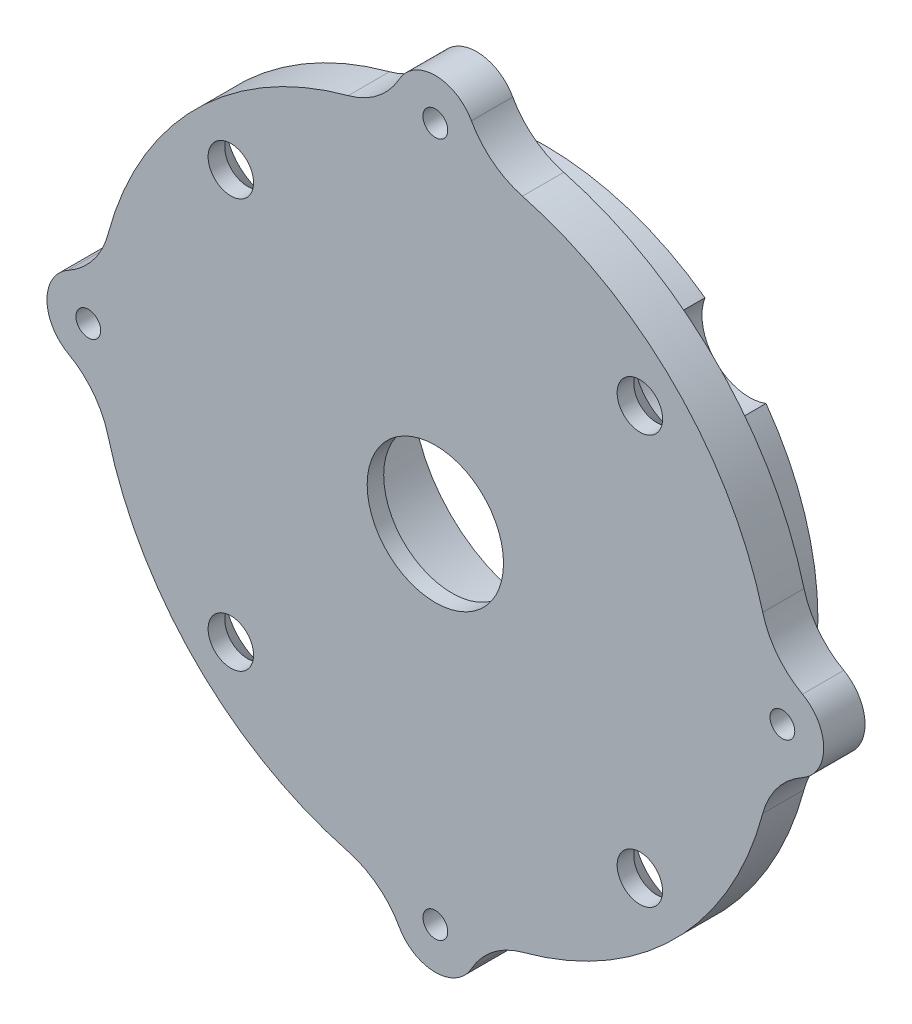
SolidWorks part; units mm, degrees
ref_plane "Ön Düzlem" through (0, 0, 0) normal (0, 0, 1) x (1, 0, 0)
ref_plane "Üst Düzlem" through (0, 0, 0) normal (0, 1, 0) x (1, 0, 0)
ref_plane "Sağ Düzlem" through (0, 0, 0) normal (1, 0, 0) x (0, 0, -1)
sketch "Çizim1" plane through (0, 0, 0) normal (0, 0, 1) x (1, 0, 0)
  circle A0 centre (0, 0) radius 16.1
  circle A1 centre (0, 0) radius 22.5
  circle A2 centre (0, 0) radius 33.05
  circle A3 centre (0, 0) radius 28
  dimension "D1" = 32.2
  dimension "D2" = 45
  dimension "D3" = 66.1
  dimension "D4" = 56
extrude "Yükseklik-Ekstrüzyon1" add sketch "Çizim1" along normal blind 8.25 contours A1 A0 | A2 A3 region at (-21.8636, 0, 0) region at (-32.1152, 0, 0)
sketch "Çizim2" plane through (0, 0, 8.25) normal (0, 0, 1) x (1, 0, 0)
  circle A0 centre (-24.75, 24.75) radius 2
  circle A1 centre (24.75, 24.75) radius 2
  circle A2 centre (24.75, -24.75) radius 2
  circle A3 centre (-24.75, -24.75) radius 2
  arc A6 (-10.5408, 39.6218) -> (-39.6218, 10.5408) centre (0, 0) ccw
  circle A7 centre (0, 42) radius 1.5
  arc A8 (4.3706, 44.4286) -> (-4.3706, 44.4286) centre (0, 42) ccw
  arc A9 (-4.3706, 44.4286) -> (-10.5408, 39.6218) centre (-13.1118, 49.2857) cw
  arc A10 (4.3706, 44.4286) -> (10.5408, 39.6218) centre (13.1118, 49.2857) ccw
  arc A11 (44.4286, 4.3706) -> (39.6218, 10.5408) centre (49.2857, 13.1118) cw
  arc A12 (44.4286, -4.3706) -> (44.4286, 4.3706) centre (42, 0) ccw
  circle A13 centre (42, 0) radius 1.5
  arc A14 (44.4286, -4.3706) -> (39.6218, -10.5408) centre (49.2857, -13.1118) ccw
  arc A15 (4.3706, -44.4286) -> (10.5408, -39.6218) centre (13.1118, -49.2857) cw
  arc A16 (-4.3706, -44.4286) -> (4.3706, -44.4286) centre (0, -42) ccw
  circle A17 centre (0, -42) radius 1.5
  arc A18 (-4.3706, -44.4286) -> (-10.5408, -39.6218) centre (-13.1118, -49.2857) ccw
  arc A19 (-44.4286, -4.3706) -> (-39.6218, -10.5408) centre (-49.2857, -13.1118) cw
  arc A20 (-44.4286, 4.3706) -> (-44.4286, -4.3706) centre (-42, 0) ccw
  circle A21 centre (-42, 0) radius 1.5
  arc A22 (-44.4286, 4.3706) -> (-39.6218, 10.5408) centre (-49.2857, 13.1118) ccw
  arc A23 (-39.6218, -10.5408) -> (-10.5408, -39.6218) centre (0, 0) ccw
  arc A24 (10.5408, -39.6218) -> (39.6218, -10.5408) centre (0, 0) ccw
  arc A25 (39.6218, 10.5408) -> (10.5408, 39.6218) centre (0, 0) ccw
  circle A26 centre (0, 0) radius 8.25
  point P0 (0, 0)
  point P17 (0, 0)
  point P48 (0, 0)
  dimension "D3" = 4
  dimension "D4" = 24.75
  dimension "D5" = 24.75
  dimension "D1" = 82
  dimension "D2" = 42
  dimension "D7" = 10
  dimension "D8" = 3
  dimension "D9" = 10
  dimension "D10" = 10
  dimension "D12" = 16.5
  dimension "D6" = 4
  dimension "D11" = 4
extrude "Yükseklik-Ekstrüzyon2" add sketch "Çizim2" along normal blind 5
hole_wizard "M5 Altıgen Alyan Havşa Başlı Vida İçin Havşa1" positions "3B Çizim1" profile "Çizim5" countersink size "M5" standard "DIN" end condition through all
sketch3d "3B Çizim1"
  line L0 (24.75, 24.75, 13.25) -> (24.75, 24.75, 8.25) construction
  line L1 (-24.75, 24.75, 13.25) -> (-24.75, 24.75, 8.25) construction
  line L2 (-24.75, -24.75, 13.25) -> (-24.75, -24.75, 8.25) construction
  line L3 (24.75, -24.75, 13.25) -> (24.75, -24.75, 8.25) construction
  point P0 (24.75, 24.75, 8.25)
  point P4 (-24.75, 24.75, 8.25)
  point P8 (-24.75, -24.75, 8.25)
  point P12 (24.75, -24.75, 8.25)
sketch "Çizim5" plane through (24.75, 24.75, 8.25) normal (1, 0, 0) x (0, 1, 0)
  line L0 (0, 0) -> (0, 5)
  line L1 (0, 5) -> (2.75, 5)
  line L2 (2.75, 5) -> (2.75, 2.985)
  line L3 (2.75, 2.985) -> (5.735, 0)
  line L5 (5.735, 0) -> (0, 0)
  line L6 (-2.75, 2.985) -> (-5.735, 0) construction
  line L11 (0, -6.35) -> (0, 107.95) construction
  dimension "Thru Hole Dia." = 5.5
  dimension "Thru Hole Depth" = 5
  dimension "Near C'Sink Dia." = 11.47
  dimension "Near C'Sink Angle" = 90
sketch "Çizim7" plane through (0, 0, 8.25) normal (0, 0, -1) x (-1, 0, 0)
  circle A0 centre (0, 0) radius 16.1 construction
  circle A1 centre (0, 0) radius 16.1
extrude "Kes-Ekstrüzyon2" cut sketch "Çizim7" against normal blind 1
sketch "Çizim8" plane through (0, 0, 0) normal (0, 0, -1) x (-1, 0, 0)
  circle A0 centre (-24.75, 24.75) radius 5.735
  circle A1 centre (24.75, 24.75) radius 5.735
  circle A2 centre (24.75, -24.75) radius 5.735
  circle A3 centre (-24.75, -24.75) radius 5.735
  arc A4 (-19.3825, 26.7698) -> (-26.7698, 19.3825) centre (-24.75, 24.75) ccw construction
  point P12 (0, 0)
  dimension "D1" = 4
extrude "Kes-Ekstrüzyon3" cut sketch "Çizim8" against normal up to surface (8.25 mm away) up to face at (0, 0, 8.25)
sketch "Çizim9" plane through (0, 0, 9.25) normal (0, 0, -1) x (-1, 0, 0)
  circle A0 centre (0, 0) radius 12.5
  dimension "D1" = 25
extrude "Kes-Ekstrüzyon4" cut sketch "Çizim9" against normal blind 2
